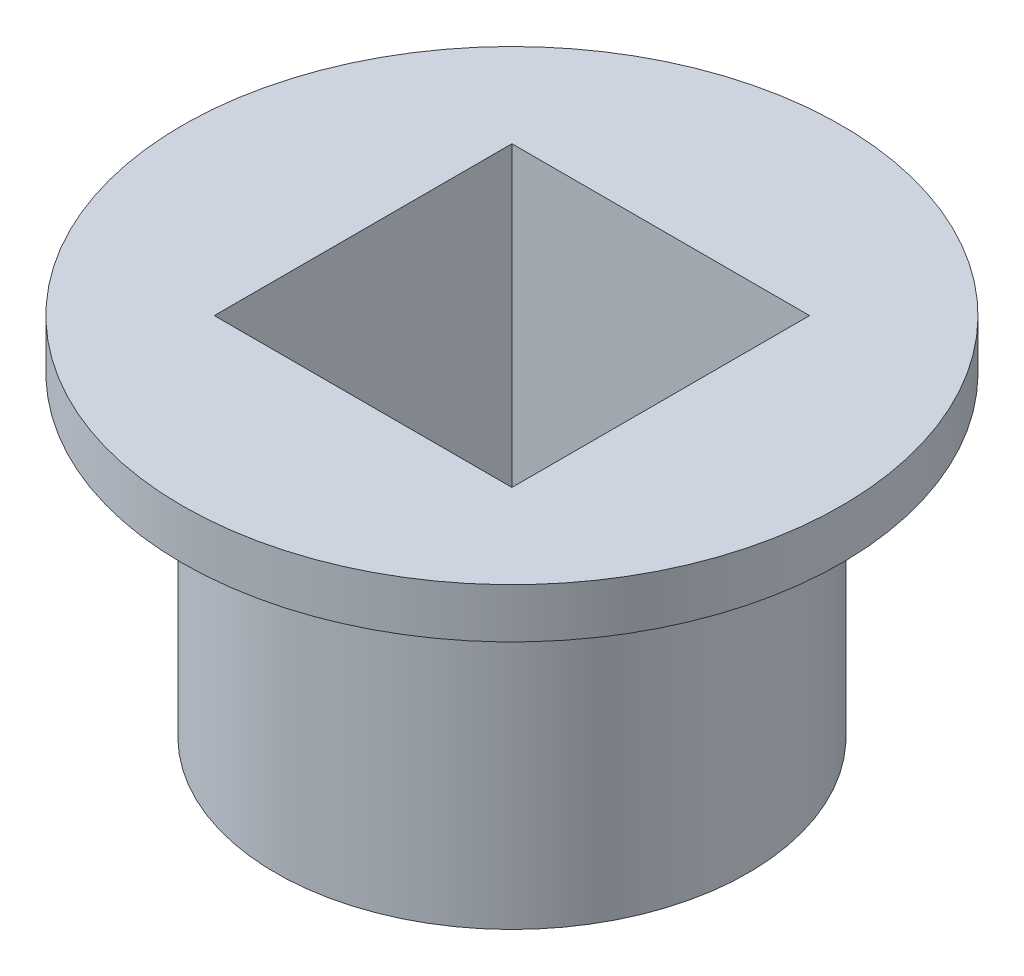
SolidWorks part; units mm, degrees
ref_plane "Front Plane" through (0, 0, 0) normal (0, 0, 1) x (1, 0, 0)
ref_plane "Top Plane" through (0, 0, 0) normal (0, 1, 0) x (1, 0, 0)
ref_plane "Right Plane" through (0, 0, 0) normal (1, 0, 0) x (0, 0, -1)
sketch "Sketch1" plane through (0, 0, 0) normal (0, 1, 0) x (1, 0, 0)
  line L0 (-6, -6) -> (6, -6)
  line L1 (-6, -6) -> (-6, 6)
  line L2 (6, -6) -> (6, 6)
  line L3 (-6, 6) -> (6, 6)
  line L4 (-6, -6) -> (6, 6) construction
  line L5 (6, -6) -> (-6, 6) construction
  circle A0 centre (0, 0) radius 9.525
  point P1 (0, 0)
  dimension "D3" = 19.05
  dimension "D1" = 12
  dimension "D2" = 12
extrude "Boss-Extrude1" add sketch "Sketch1" along normal blind 12.7
sketch "Sketch2" plane through (0, 12.7, 0) normal (0, 1, 0) x (1, 0, 0)
  circle A1 centre (0, 0) radius 9.525 construction
  circle A3 centre (0, 0) radius 13.2875
  circle A4 centre (0, 0) radius 9.525
  dimension "D1" = 26.575
extrude "Boss-Extrude3" add sketch "Sketch2" against normal blind 2
sketch "Sketch3" plane through (0, 0, 0) normal (0, -1, 0) x (1, 0, 0)
  circle A0 centre (0, 0) radius 9.525 construction
  circle A1 centre (0, 0) radius 9.525
  circle A2 centre (0, 0) radius 4.5
  dimension "D1" = 9
extrude "Boss-Extrude4" add sketch "Sketch3" along normal blind 2
